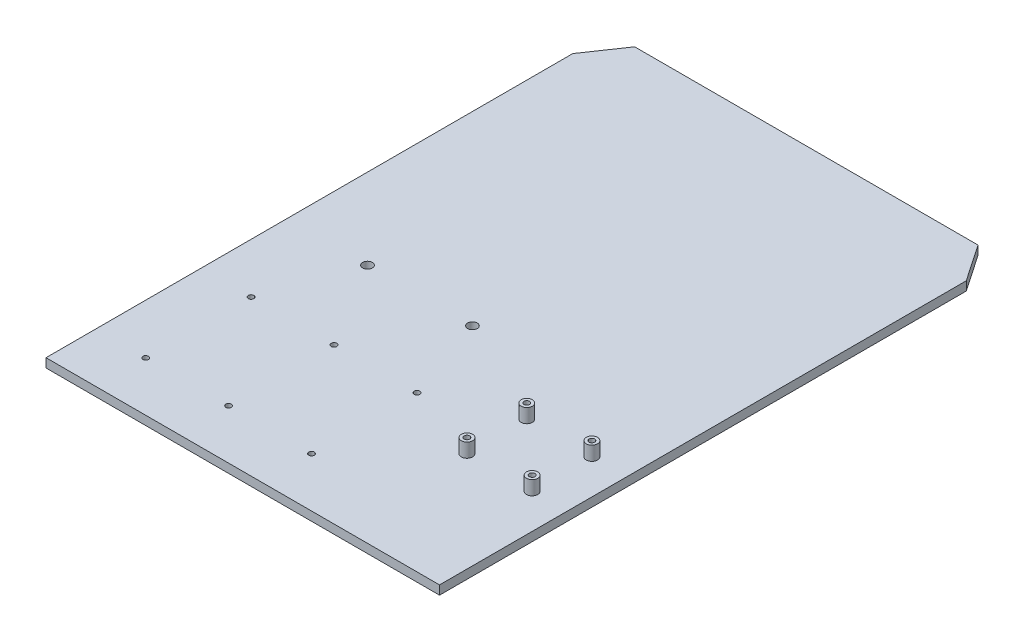
SolidWorks part; units mm, degrees
ref_plane "Front Plane" through (0, 0, 0) normal (0, 0, 1) x (1, 0, 0)
ref_plane "Top Plane" through (0, 0, 0) normal (0, 1, 0) x (1, 0, 0)
ref_plane "Right Plane" through (0, 0, 0) normal (1, 0, 0) x (0, 0, -1)
sketch "Sketch2" plane through (0, 0, 0) normal (0, 1, 0) x (1, 0, 0)
  line L0 (0, 0) -> (280, 0)
  line L1 (280, 0) -> (280, 374.8)
  line L2 (0, 0) -> (20, 0) construction
  line L3 (280, 374.8) -> (262.1427, 401.0063)
  line L4 (140, 401.01) -> (262.1427, 401.0063)
  line L5 (0, 374.8) -> (17.8573, 401.0063)
  line L6 (0, 0) -> (0, 374.8)
  line L7 (140, 401.01) -> (17.8573, 401.0063)
  line L8 (0, 0) -> (35.4673, 35.2427) construction
  circle A0 centre (35.5904, 35.365) radius 2
  circle A1 centre (35.5904, 110.365) radius 2
  circle A2 centre (94.5904, 35.365) radius 2
  circle A3 centre (94.5904, 110.365) radius 2
  circle A4 centre (153.5904, 35.365) radius 2
  circle A5 centre (153.5904, 110.365) radius 2
  circle A6 centre (57.3824, 171.3778) radius 3.455
  circle A7 centre (132.0324, 171.3778) radius 3.455
extrude "Boss-Extrude1" add sketch "Sketch2" along normal blind 6.35
sketch "Sketch3" plane through (0, 6.35, 0) normal (0, 1, 0) x (1, 0, 0)
  circle A2 centre (208.928, 90.6123) radius 2
  circle A3 centre (255.283, 90.6123) radius 2
  circle A4 centre (255.283, 133.1573) radius 2
  circle A5 centre (208.928, 133.1573) radius 2
  circle A6 centre (208.928, 90.6123) radius 4
  circle A7 centre (208.928, 133.1573) radius 4
  circle A8 centre (255.283, 133.1573) radius 4
  circle A9 centre (255.283, 90.6123) radius 4
extrude "Boss-Extrude2" add sketch "Sketch3" along normal blind 10
